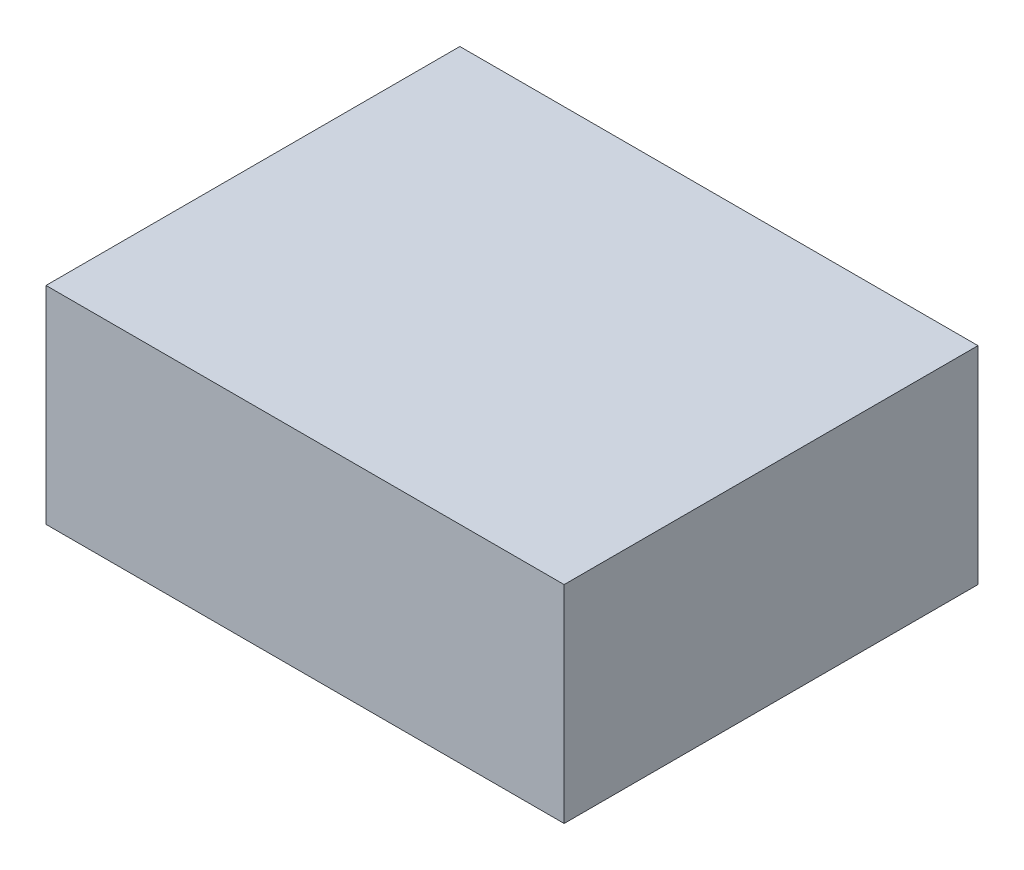
SolidWorks part; units mm, degrees
ref_plane "Front Plane" through (0, 0, 0) normal (0, 0, 1) x (1, 0, 0)
ref_plane "Top Plane" through (0, 0, 0) normal (0, 1, 0) x (1, 0, 0)
ref_plane "Right Plane" through (0, 0, 0) normal (1, 0, 0) x (0, 0, -1)
sketch "Sketch1" plane through (0, 0, 0) normal (0, 1, 0) x (1, 0, 0)
  line L1 (15.9, 12.7) -> (-15.9, 12.7)
  line L2 (15.9, 12.7) -> (15.9, -12.7)
  line L3 (15.9, -12.7) -> (-15.9, -12.7)
  line L4 (-15.9, 12.7) -> (-15.9, -12.7)
  line L5 (15.9, 12.7) -> (-15.9, -12.7) construction
  line L6 (15.9, -12.7) -> (-15.9, 12.7) construction
  point P0 (0, 0)
extrude "Boss-Extrude1" add sketch "Sketch1" along normal blind 12.7
sketch "Sketch2" plane through (0, 0, 0) normal (0, -1, 0) x (1, 0, 0)
  line L0 (0, 0) -> (14, 0) construction
  line L1 (0, 0) -> (0, 9.38) construction
  line L2 (0, 0) -> (-14, 0) construction
  line L3 (-14, 0) -> (14, 0)
  ellipse E0 centre (0, 0) end of major axis (-14, 0) minor radius 9.38 (0, 9.38) -> (14, 0) cw
  ellipse E1 centre (0, 0) end of major axis (-14, 0) minor radius 9.38 (0, 9.38) -> (-14, 0) ccw
  dimension "D1" = 9.38
  dimension "D2" = 14
  dimension "D3" = 14
